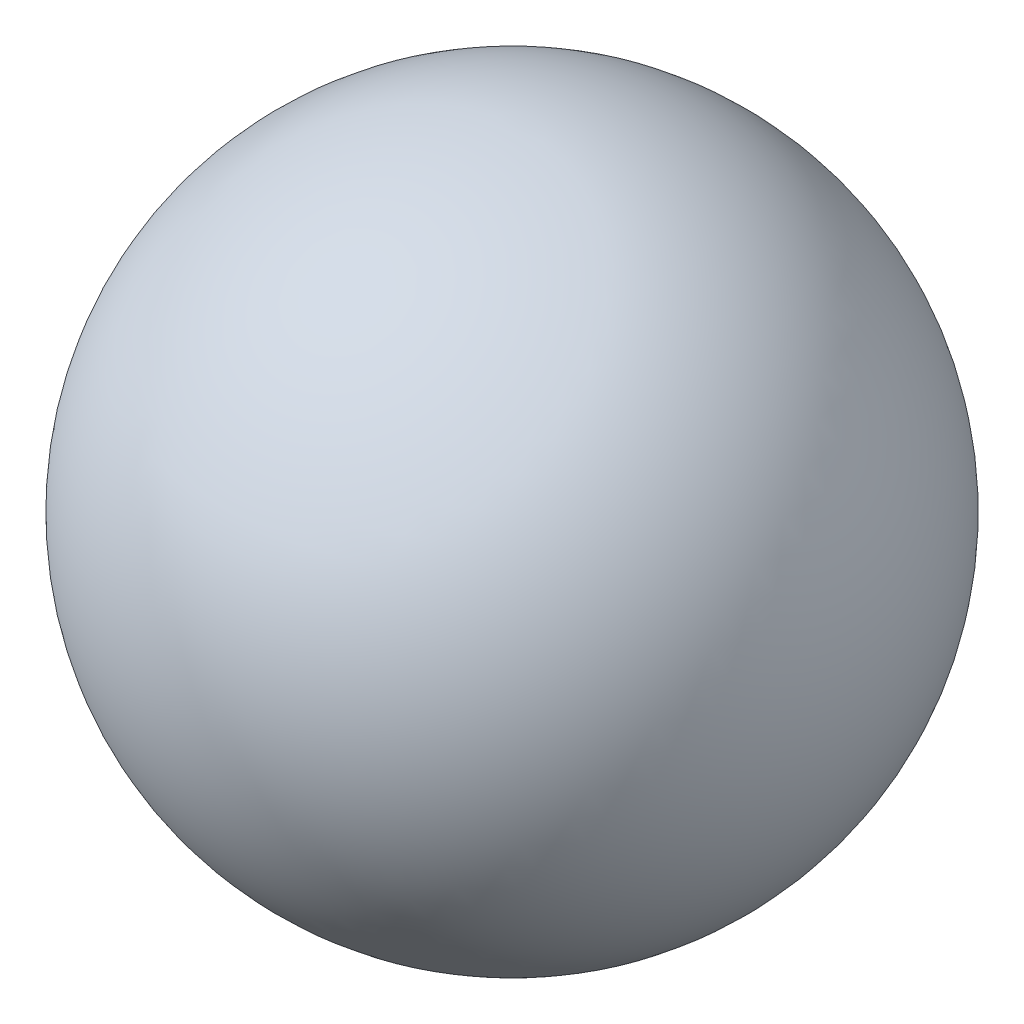
SolidWorks part; units mm, degrees
ref_plane "Front Plane" through (0, 0, 0) normal (0, 0, 1) x (1, 0, 0)
ref_plane "Top Plane" through (0, 0, 0) normal (0, 1, 0) x (1, 0, 0)
ref_plane "Right Plane" through (0, 0, 0) normal (1, 0, 0) x (0, 0, -1)
sketch "Sketch1" plane through (0, 0, 0) normal (0, 0, 1) x (1, 0, 0)
  line L0 (0, 0) -> (0, 15)
  line L1 (0, 15) -> (0, -15)
  circle A0 centre (0, 0) radius 15
  dimension "D1" = 15
  dimension "D2" = 30
revolve "Revolve1" add sketch "Sketch1" angle 360 about L1 region at (-6.3662, 0, 0)
